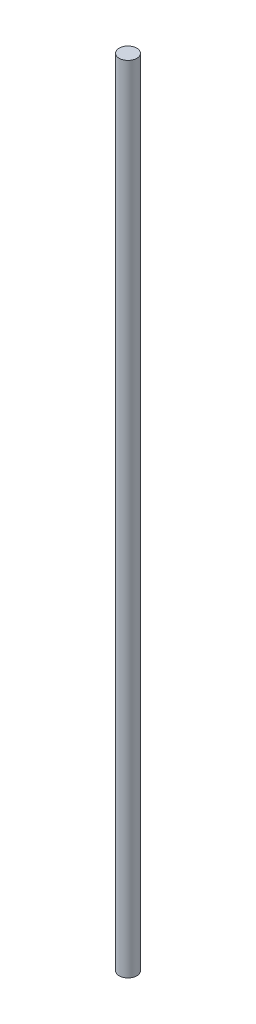
SolidWorks part; units mm, degrees
material "AISI 1020"
ref_plane "Front Plane" through (0, 0, 0) normal (0, 0, 1) x (1, 0, 0)
ref_plane "Top Plane" through (0, 0, 0) normal (0, 1, 0) x (1, 0, 0)
ref_plane "Right Plane" through (0, 0, 0) normal (1, 0, 0) x (0, 0, -1)
sketch "Sketch1" plane through (0, 0, 0) normal (0, 1, 0) x (1, 0, 0)
  circle A0 centre (0, 0) radius 4
  dimension "D1" = 8
extrude "Boss-Extrude1" add sketch "Sketch1" along normal blind 180 and the other way blind 180
cosmetic thread "Cosmetic Thread1" parameters "D2"=7
